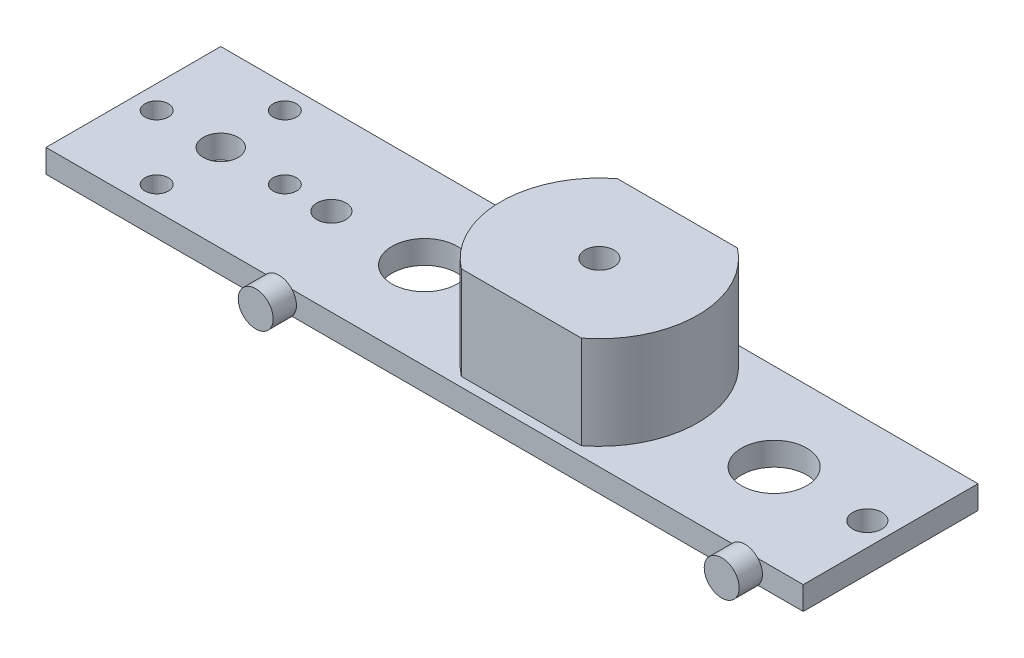
SolidWorks part; units mm, degrees
ref_plane "前视基准面" through (0, 0, 0) normal (0, 0, 1) x (1, 0, 0)
ref_plane "上视基准面" through (0, 0, 0) normal (0, 1, 0) x (1, 0, 0)
ref_plane "右视基准面" through (0, 0, 0) normal (1, 0, 0) x (0, 0, -1)
other "Configuration Table"
sketch "草图1" plane through (0, 0, 0) normal (0, 1, 0) x (1, 0, 0)
  line L0 (0, 7.5) -> (0, -7.5) construction
  line L1 (-25, 7.5) -> (25, 7.5)
  line L2 (-25, 7.5) -> (-25, -7.5)
  line L3 (-25, -7.5) -> (25, -7.5)
  line L4 (25, 7.5) -> (25, -7.5)
  line L5 (-25, 0) -> (25, 0) construction
  line L7 (-25, -7.5) -> (-40, -7.5)
  line L10 (-25, -7.5) -> (-25, 7.5)
  line L11 (-25, 7.5) -> (-40, 7.5)
  line L12 (-40, -7.5) -> (-40, 7.5)
  line L14 (-25, 7.5) -> (-40, 7.5)
  dimension "D1" = 50
  dimension "D2" = 15
  dimension "D6" = 15
  dimension "D7" = 15
extrude "凸台-拉伸1" add sketch "草图1" along normal blind 2 contours L11 L2 | L2 L1 L4 L3 | L10 L7 L12 L11 region at (-32.5, 0, 0)
sketch "草图2" plane through (0, 0, 0) normal (0, 1, 0) x (1, 0, 0)
  line L0 (0, 7.5) -> (0, -7.5) construction
  line L1 (25, 7.5) -> (-40, 7.5) construction
  line L2 (-32.5, 7.5) -> (-32.5, -7.5) construction
  line L3 (-40, -7.5) -> (-40, 7.5) construction
  line L4 (-25, 7.5) -> (-25, -7.5) construction
  line L6 (-25, -7.5) -> (25, -7.5) construction
  line L10 (-40, 0) -> (-25, 0) construction
  line L14 (-40, -7.5) -> (25, -7.5) construction
  circle A2 centre (0, 0) radius 1.25
  circle A3 centre (15, 0) radius 4.1
  circle A4 centre (15, 0) radius 2.8
  circle A5 centre (-15, 0) radius 4.1
  circle A6 centre (-15, 0) radius 2.8
  circle A8 centre (23, 0) radius 1.25
  circle A9 centre (-23, 0) radius 1.25
  circle A11 centre (-32.5, 0) radius 1.5
  circle A12 centre (-27, 0) radius 1
  circle A13 centre (-32.5, -5.5) radius 1
  circle A14 centre (-38, 0) radius 1
  circle A15 centre (-32.5, 5.5) radius 1
  point P36 (0, -7.5)
  dimension "D3" = 2.5
  dimension "D4" = 5.6
  dimension "D5" = 8.2
  dimension "D7" = 15
  dimension "D8" = 2.5
  dimension "D11" = 3
  dimension "D12" = 2
  dimension "D2" = 7.5
  dimension "D6" = 15
  dimension "D10" = 8
  dimension "D13" = 5.5
  dimension "D17" = 7.5
  dimension "D14" = 4
extrude "切除-拉伸1" cut sketch "草图2" along normal up to surface (2 mm away) contours A2 | A9 | A8 | A6 | A4 | A14 | A11 | A13 | A12 | A15 up to face at (-7.5, 2, 0)
sketch "草图4" plane through (0, 0, 7.5) normal (0, 0, 1) x (1, 0, 0)
  line L0 (25, 1) -> (-40, 1) construction
  line L1 (25, 2) -> (25, 0) construction
  line L2 (-40, 2) -> (-40, 0) construction
  line L3 (0, 0) -> (0, 2) construction
  line L5 (25, 2) -> (25, 0) construction
  line L6 (-40, 2) -> (25, 2) construction
  circle A0 centre (20, 1) radius 1.5
  circle A1 centre (-20, 1) radius 1.5
  dimension "D1" = 3
  dimension "D2" = 3
  dimension "D3" = 20
  dimension "D4" = 20
  dimension "D5" = 25
extrude "凸台-拉伸2" add sketch "草图4" along normal blind 2
sketch "草图5" plane through (0, 2, 0) normal (0, 1, 0) x (1, 0, 0)
  line L0 (0, 0) -> (0, 4.126) construction
  line L1 (4.9054, -6) -> (-4.9054, -6)
  line L2 (-4.7026, 0) -> (-2.9861, 0) construction
  line L3 (4.9054, 6) -> (-4.9054, 6)
  line L4 (5.149, -6.7) -> (-5.149, -6.7)
  line L5 (5.149, 6.7) -> (-5.149, 6.7)
  arc A0 (-4.9054, 6) -> (-4.9054, -6) centre (0, 0) ccw
  arc A1 (4.9054, -6) -> (4.9054, 6) centre (0, 0) ccw
  arc A2 (-5.149, 6.7) -> (-5.149, -6.7) centre (0, 0) ccw
  arc A3 (5.149, -6.7) -> (5.149, 6.7) centre (0, 0) ccw
  point P14 (0, -6)
  point P15 (0, 6)
  point P21 (0, -6.7)
  point P22 (0, 6.7)
  circle M9 centre (0, 0) radius 1.25
  dimension "D1" = 15.5
  dimension "D3" = 16.9
  dimension "D2" = 12
  dimension "D4" = 13.4
extrude "凸台-拉伸3" add sketch "草图5" along normal blind 8
extrude "凸台-拉伸4" add sketch "草图5<8>" along direction (0, 1, 0) on the side of the normal up to surface (8 mm away) contours L1 A1 L3 A0 M9 region at (0, 2, 5.804) up to face at (0, 10, 0)
sketch "草图5<8>" plane through (0, 2, 0) normal (0, 1, 0) x (1, 0, 0) same geometry as "草图5"
extrude "切除-拉伸2" cut sketch "草图5<11>" against normal through all and the other way offset from surface 2.5 contours L1 A1 L3 A0 M9 region at (0, 2, 5.804) other way up to face at (0, 10, 0)
sketch "草图5<11>" plane through (0, 2, 0) normal (0, 1, 0) x (1, 0, 0) same geometry as "草图5"
